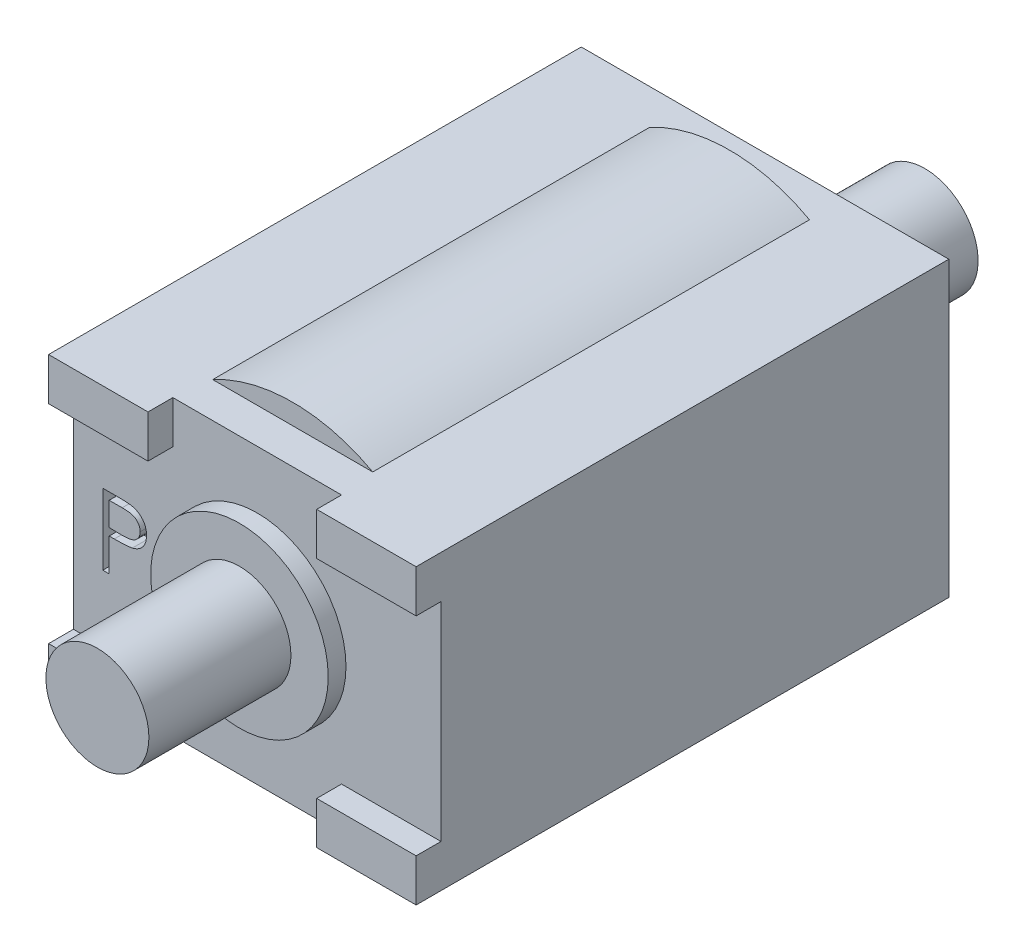
SolidWorks part; units mm, degrees
ref_plane "Front Plane" through (0, 0, 0) normal (0, 0, 1) x (1, 0, 0)
ref_plane "Top Plane" through (0, 0, 0) normal (0, 1, 0) x (1, 0, 0)
ref_plane "Right Plane" through (0, 0, 0) normal (1, 0, 0) x (0, 0, -1)
sketch "Sketch1" plane through (0, 0, 0) normal (0, 0, 1) x (1, 0, 0)
  line L0 (-5.175, -4.125) -> (5.175, -4.125)
  line L1 (-5.175, -4.125) -> (-5.175, 4.125)
  line L2 (5.175, -4.125) -> (5.175, 4.125)
  line L3 (-5.175, 4.125) -> (5.175, 4.125)
  line L4 (-5.175, -4.125) -> (5.175, 4.125) construction
  line L5 (5.175, -4.125) -> (-5.175, 4.125) construction
  point P1 (0, 0)
  dimension "D1" = 8.25
  dimension "D2" = 10.35
extrude "Boss-Extrude1" add sketch "Sketch1" along normal blind 14.3
sketch "Sketch2" plane through (0, 0, 14.3) normal (0, 0, 1) x (1, 0, 0)
  circle A0 centre (0, 0) radius 2.5
  dimension "D1" = 5
extrude "Boss-Extrude2" add sketch "Sketch2" along normal blind 0.5
sketch "Sketch3" plane through (0, 0, 14.3) normal (0, 0, 1) x (1, 0, 0)
  circle A0 centre (0, 0) radius 1.45
  dimension "D1" = 2.9
extrude "Boss-Extrude3" add sketch "Sketch3" along normal blind 4.5
sketch "Sketch4" plane through (0, 0, 14.3) normal (0, 0, 1) x (1, 0, 0)
  line L0 (0, 0) -> (0, 1.8465) construction
  line L1 (-5.175, 4.125) -> (-2.375, 4.125)
  line L2 (-5.175, 4.125) -> (-5.175, 2.925)
  line L3 (-5.175, 2.925) -> (-2.375, 2.925)
  line L4 (-2.375, 4.125) -> (-2.375, 2.925)
  line L9 (0, 0) -> (2.0189, 0) construction
  line L10 (5.175, 2.925) -> (2.375, 2.925)
  line L11 (2.375, 4.125) -> (2.375, 2.925)
  line L12 (5.175, 4.125) -> (2.375, 4.125)
  line L13 (5.175, 4.125) -> (5.175, 2.925)
  line L14 (-5.175, -2.925) -> (-2.375, -2.925)
  line L15 (-2.375, -4.125) -> (-2.375, -2.925)
  line L16 (-5.175, -4.125) -> (-2.375, -4.125)
  line L17 (-5.175, -4.125) -> (-5.175, -2.925)
  line L18 (5.175, -4.125) -> (5.175, -2.925)
  line L19 (5.175, -4.125) -> (2.375, -4.125)
  line L20 (2.375, -4.125) -> (2.375, -2.925)
  line L21 (5.175, -2.925) -> (2.375, -2.925)
  dimension "D1" = 1.2
  dimension "D2" = 2.8
extrude "Boss-Extrude4" add sketch "Sketch4" along normal blind 0.7
sketch "Sketch5" plane through (0, 0, 14.3) normal (0, 0, 1) x (1, 0, 0)
  text T0 "P" font "Century Gothic" height 2
extrude "Cut-Extrude1" cut sketch "Sketch5" against normal blind 0.5
sketch "Sketch6" plane through (0, 0, 0) normal (0, 0, -1) x (-1, 0, 0)
  circle A0 centre (0, 0) radius 1.5
  dimension "D1" = 3
extrude "Boss-Extrude5" add sketch "Sketch6" along normal blind 4.5
sketch "Sketch7" plane through (0, 0, 0) normal (0, 0, -1) x (-1, 0, 0)
  circle A0 centre (0, 0) radius 1.9
  dimension "D1" = 3.8
extrude "Boss-Extrude6" add sketch "Sketch7" along normal blind 0.3
sketch "Sketch8" plane through (0, 0, 0) normal (0, 0, -1) x (-1, 0, 0)
  text T0 "m" font "Century Gothic" height 2
extrude "Cut-Extrude2" cut sketch "Sketch8" against normal blind 0.5
sketch "Sketch9" plane through (0, 0, 0) normal (0, 0, -1) x (-1, 0, 0)
  circle A0 centre (0, 0) radius 4.7
  dimension "D1" = 9.4
extrude "Boss-Extrude7" add sketch "Sketch9" against normal offset from surface (12.3 mm away) 1 from offset 1 up to face at (0, 0, 14.3) offset against normal yes
